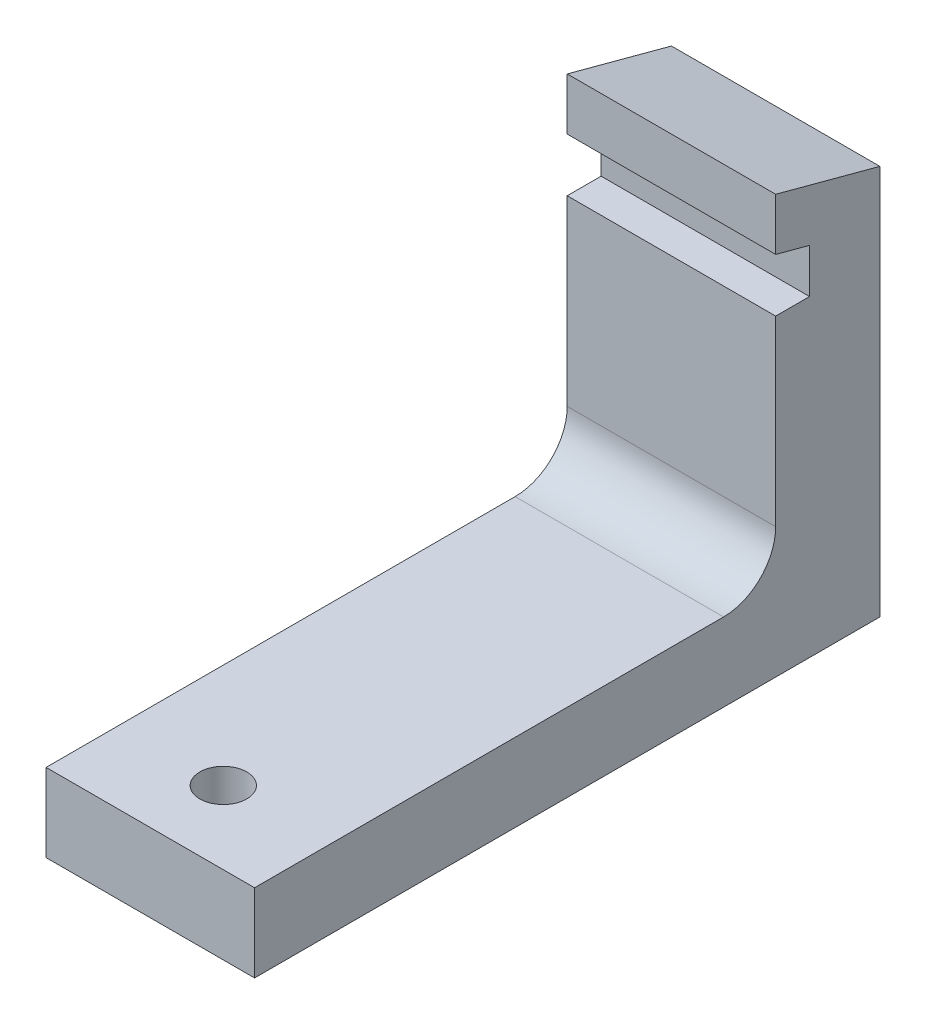
SolidWorks part; units mm, degrees
ref_plane "Front" through (0, 0, 0) normal (0, 0, 1) x (1, 0, 0)
ref_plane "Top" through (0, 0, 0) normal (0, 1, 0) x (1, 0, 0)
ref_plane "Right" through (0, 0, 0) normal (1, 0, 0) x (0, 0, -1)
ref_axis "X" through (-80.9, 0, 0) along (1, 0, 0)
ref_axis "Y" through (0, -50, 0) along (0, 1, 0)
ref_axis "Z" through (0, 0, -80.9) along (0, 0, 1)
sketch "Sketch1" plane through (0, 0, 0) normal (1, 0, 0) x (0, 0, -1)
  line L0 (0, 3) -> (20, 3)
  line L1 (20, 3) -> (20, 12)
  line L2 (0, 0) -> (24, 0)
  line L3 (0, 3) -> (0, 0)
  line L4 (24, 0) -> (24, 14.9765)
  line L6 (20, 12) -> (21.3, 12)
  line L7 (21.3, 12) -> (21.3, 13.7)
  line L8 (21.3, 13.7) -> (20, 14.0483)
  line L9 (20, 14.0483) -> (20, 16.0483)
  line L10 (20, 16.0483) -> (24, 14.9765)
  point P11 (0, 0)
  dimension "D1" = 15
  dimension "D2" = 1.7
  dimension "D3" = 3
  dimension "D4" = 1.3
  dimension "D5" = 4
  dimension "D6" = 12
  dimension "D7" = 2
  dimension "D8" = 24
extrude "Boss-Extrude1" add sketch "Sketch1" along normal mid plane 8
fillet "Fillet1" radius 2 1 edges at (0, 3, -20)
sketch "Sketch2" plane through (0, 0, 0) normal (0, -1, 0) x (1, 0, 0)
  line L0 (0, -2.8) -> (0, -20.8) construction
  line L1 (0, -20.8) -> (0, -24) construction
  line L2 (4, -24) -> (-4, -24) construction
  circle A0 centre (0, -20.8) radius 0.9
  circle A1 centre (0, -2.8) radius 0.9
  dimension "D3" = 1.8
  dimension "D1" = 3.2
  dimension "D2" = 18
extrude "Cut-Extrude1" cut sketch "Sketch2" against normal blind 4
